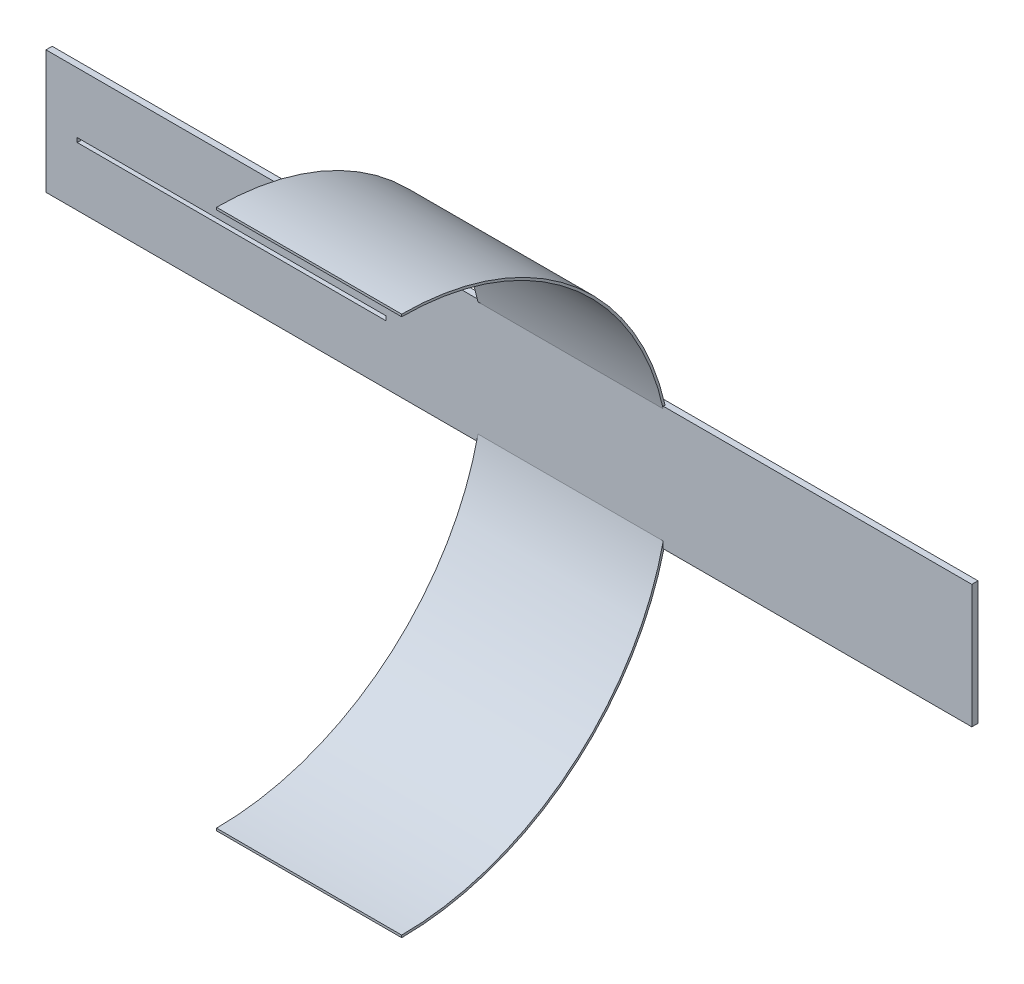
SolidWorks part; units mm, degrees
ref_plane "Front Plane" through (0, 0, 0) normal (0, 0, 1) x (1, 0, 0)
ref_plane "Top Plane" through (0, 0, 0) normal (0, 1, 0) x (1, 0, 0)
ref_plane "Right Plane" through (0, 0, 0) normal (1, 0, 0) x (0, 0, -1)
sketch "Szkic4" plane through (0, 0, 0) normal (0, 0, 1) x (1, 0, 0)
  line L0 (-0.0618, 10.1285) -> (-0.0618, -9.8715) construction
  line L1 (-30.0618, 10.1285) -> (119.9382, 10.1285)
  line L2 (-30.0618, 10.1285) -> (-30.0618, -9.8715)
  line L3 (-30.0618, -9.8715) -> (119.9382, -9.8715)
  line L4 (119.9382, 10.1285) -> (119.9382, -9.8715)
  line L6 (-25, -0.35) -> (25, -0.35)
  line L7 (-25, -0.35) -> (-25, 0.35)
  line L8 (-25, 0.35) -> (25, 0.35)
  line L9 (25, -0.35) -> (25, 0.35)
  line L10 (-25, -0.35) -> (25, 0.35) construction
  line L11 (-25, 0.35) -> (25, -0.35) construction
  point P6 (0, 0)
  dimension "D1" = 20
  dimension "D2" = 150
  dimension "D3" = 30
extrude "Dodanie-wyciągnięcie1" add sketch "Szkic4" along normal blind 1
sketch "Szkic6" plane through (0, 0, 1) normal (0, 0, 1) x (1, 0, 0)
  line L0 (119.9382, 0.1285) -> (69.9382, 0.1285) construction
  line L1 (119.9382, -9.8715) -> (119.9382, 10.1285) construction
ref_plane "Płaszczyzna1" through (69.9382, 0, 0) normal (1, 0, 0) x (0, 0, -1)
sketch "Szkic8" plane through (69.9382, 0, 0) normal (1, 0, 0) x (0, 0, -1)
  line L0 (-43.3742, 44.7493) -> (-43.3742, -43.7885)
  circle A0 centre (-43.3742, 0.4804) radius 43.75
  circle A1 centre (-43.3742, 0.4804) radius 43.3768
  point P7 (-43.3742, 0.4804)
extrude "Dodanie-wyciągnięcie2" add sketch "Szkic8" against normal blind 30 contours A1 L0 A0 region at (69.9382, 31.3471, 12.5074)
